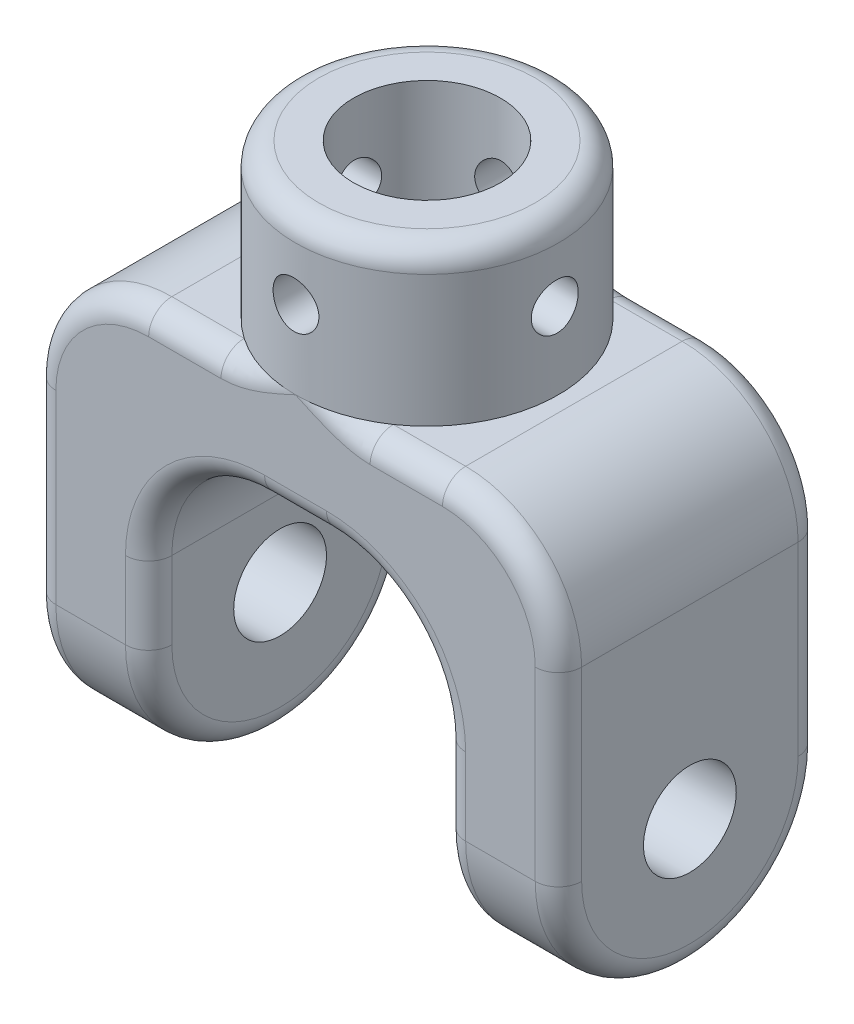
SolidWorks part; units mm, degrees
material "Gray Cast Iron"
ref_plane "Front Plane" through (0, 0, 0) normal (0, 0, 1) x (1, 0, 0)
ref_plane "Top Plane" through (0, 0, 0) normal (0, 1, 0) x (1, 0, 0)
ref_plane "Right Plane" through (0, 0, 0) normal (1, 0, 0) x (0, 0, -1)
sketch "Sketch1" plane through (0, 0, 0) normal (1, 0, 0) x (0, 0, -1)
  line L0 (0, -33.5755) -> (0, 30.8317) construction
  line L1 (-17, 0) -> (-17, 39)
  line L2 (-17, 39) -> (17, 39)
  line L3 (17, 39) -> (17, 0)
  arc A0 (-17, 0) -> (17, 0) centre (0, 0) ccw
  circle A1 centre (0, 0) radius 6
  point P10 (0, -17)
  point P11 (0, 39)
  dimension "D1" = 12
  dimension "D2" = 34
  dimension "D3" = 56
extrude "Boss-Extrude1" add sketch "Sketch1" along normal blind 68
sketch "Sketch2" plane through (0, 39, 0) normal (0, 1, 0) x (1, 0, 0)
  line L0 (0, 0) -> (77.5921, 0) construction
  line L1 (34, -17) -> (34, 19.7672) construction
  line L2 (68, -17) -> (0, -17) construction
  circle A0 centre (34, 0) radius 17
  dimension "D1" = 34
extrude "Boss-Extrude2" add sketch "Sketch2" along normal blind 20
fillet "Fillet1" radius 15 2 edges at (68, 39, 0) (0, 39, 0)
sketch "Sketch3" plane through (0, 0, 17) normal (0, 0, 1) x (1, 0, 0)
  line L0 (53, -17) -> (53, 10)
  line L1 (0, -17) -> (68, -17) construction
  line L2 (38, 25) -> (30, 25)
  line L3 (15, 10) -> (15, -17)
  line L4 (15, -17) -> (15, -21.0055)
  line L5 (15, -21.0055) -> (53, -21.0055)
  line L6 (53, -21.0055) -> (53, -17)
  line L7 (0, 0) -> (0, -17) construction
  line L8 (68, -17) -> (68, 0) construction
  arc A0 (53, 10) -> (38, 25) centre (38, 10) ccw
  arc A1 (15, 10) -> (30, 25) centre (30, 10) cw
  point P12 (68, -8.5)
  point P17 (15, 25)
  dimension "D4" = 15
  dimension "D1" = 42
  dimension "D2" = 15
  dimension "D3" = 15
extrude "Cut-Extrude1" cut sketch "Sketch3" against normal blind 102
fillet "Fillet2" radius 3 27 edges at (53, 5, 17) (48.6066, 20.6066, 17) (34, 25, 17) (19.3934, 20.6066, 17) (15, 5, 17) (15, -17, 0) (15, 5, -17) (19.3934, 20.6066, -17) (34, 25, -17) (48.6066, 20.6066, -17) (53, 5, -17) (0, 12, 17) (4.3934, 34.6066, 17) (24.5, 39, 17) (43.5, 39, 17) (63.6066, 34.6066, 17) (68, 12, 17) (68, -17, 0) (68, 12, -17) (63.6066, 34.6066, -17) (43.5, 39, -17) (24.5, 39, -17) (4.3934, 34.6066, -17) (0, 12, -17) (53, -17, 0) (34, 59, 17) (0, -17, 0)
hole_wizard "Ø19.0 (19) Diameter Hole1" positions "Sketch6" profile "Sketch7" hole size "Ø19.0" standard "ISO"
sketch "Sketch6" plane through (0, 59, 0) normal (0, 1, 0) x (1, 0, 0)
  point P0 (34, 0)
sketch "Sketch7" plane through (34, 59, 0) normal (1, 0, 0) x (0, 0, 1)
  line L0 (0, 0) -> (0, 56.0282)
  line L1 (0, 56.0282) -> (9.5, 50.32)
  line L2 (9.5, 50.32) -> (9.5, 0)
  line L5 (9.5, 0) -> (0, 0)
  line L10 (0, 56.0282) -> (-9.5, 50.32) construction
  line L11 (0, -6.35) -> (0, 107.95) construction
  dimension "Hole Dia." = 19
  dimension "Hole Depth" = 50.32
  dimension "Drill Angle" = 118
hole_wizard "Ø6.0 (6) Diameter Hole1" positions "3DSketch2" profile "Sketch9" hole size "Ø6.0" standard "ISO"
sketch3d "3DSketch2"
  point P0 (33.7863, 48.9977, 16.9987)
  dimension "D1" = 10
sketch "Sketch9" plane through (33.7863, 48.9977, 16.9987) normal (0, 1, 0) x (0.9999, 0, 0.0126)
  line L0 (0, 0) -> (0, 52.1226)
  line L1 (0, 52.1226) -> (3, 50.32)
  line L2 (3, 50.32) -> (3, 0)
  line L5 (3, 0) -> (0, 0)
  line L10 (0, 52.1226) -> (-3, 50.32) construction
  line L11 (0, -6.35) -> (0, 107.95) construction
  dimension "Hole Dia." = 6
  dimension "Hole Depth" = 50.32
  dimension "Drill Angle" = 118
pattern_circular "CirPattern1" count 2 every 90 about axis through (34, 56, 0) along (0, -1, 0) of "Ø6.0 (6) Diameter Hole1"
